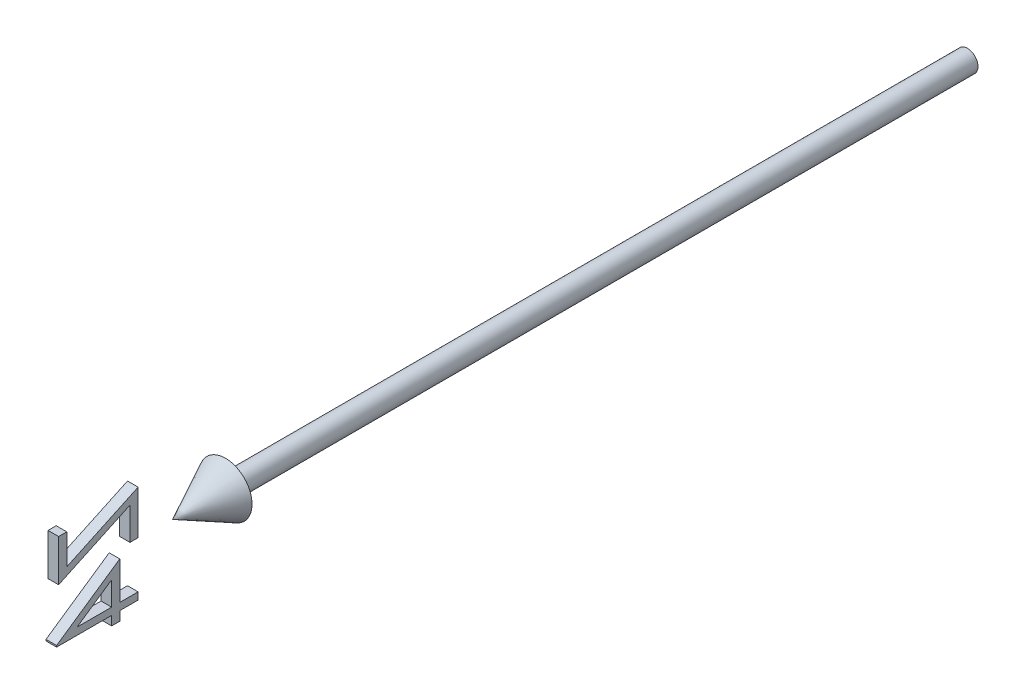
SolidWorks part; units mm, degrees
ref_plane "Front Plane" through (0, 0, 0) normal (0, 0, 1) x (1, 0, 0)
ref_plane "Top Plane" through (0, 0, 0) normal (0, 1, 0) x (1, 0, 0)
ref_plane "Right Plane" through (0, 0, 0) normal (1, 0, 0) x (0, 0, -1)
sketch "Sketch2" plane through (0, 0, 0) normal (0, 1, 0) x (1, 0, 0)
  line L0 (0, 41.95) -> (0, -114.4521) construction
  line L1 (-36.8894, 0) -> (41.4965, 0) construction
  line L2 (0, -150) -> (5, -140)
  line L3 (5, -140) -> (2, -140)
  line L4 (2, -140) -> (2, 0)
  line L5 (2, 0) -> (0, 0)
  line L6 (0, 0) -> (0, -150)
  dimension "D1" = 150
  dimension "D2" = 2
  dimension "D3" = 10
  dimension "D4" = 5
revolve "Revolve1" add sketch "Sketch2" angle 360 about L0
sketch "Sketch3" plane through (0, 0, 0) normal (1, 0, 0) x (0, -1, 0)
  line L0 (0, -101.5706) -> (0, -127.8138) construction
  line L1 (-10.1124, -157.5) -> (14.1256, -157.5) construction
  line L2 (-19.7795, 0) -> (24.9254, 0) construction
  text T0 "Z4\r\n" font "Century Gothic" height 15
  dimension "D1" = 157.5
extrude "Boss-Extrude1" add sketch "Sketch3" against normal blind 1 and the other way blind 1 separate body
equation "\"D1@Sketch2\"=\"frame_arrow_length\""
equation "\"D2@Sketch2\"=\"frame_arrow_odA\"/2"
equation "\"D4@Sketch2\"=\"frame_arrow_head_od\""
equation "\"D3@Sketch2\"=\"frame_arrow_head_length\""
equation "\"frame_arrow_length\"=150"
equation "\"frame_arrow_head_length\"=10"
equation "\"frame_arrow_head_od\"=5"
equation "\"frame_arrow_odA\"=4"
equation "\"D1@Sketch3\"=\"frame_arrow_length\"*1.05"
